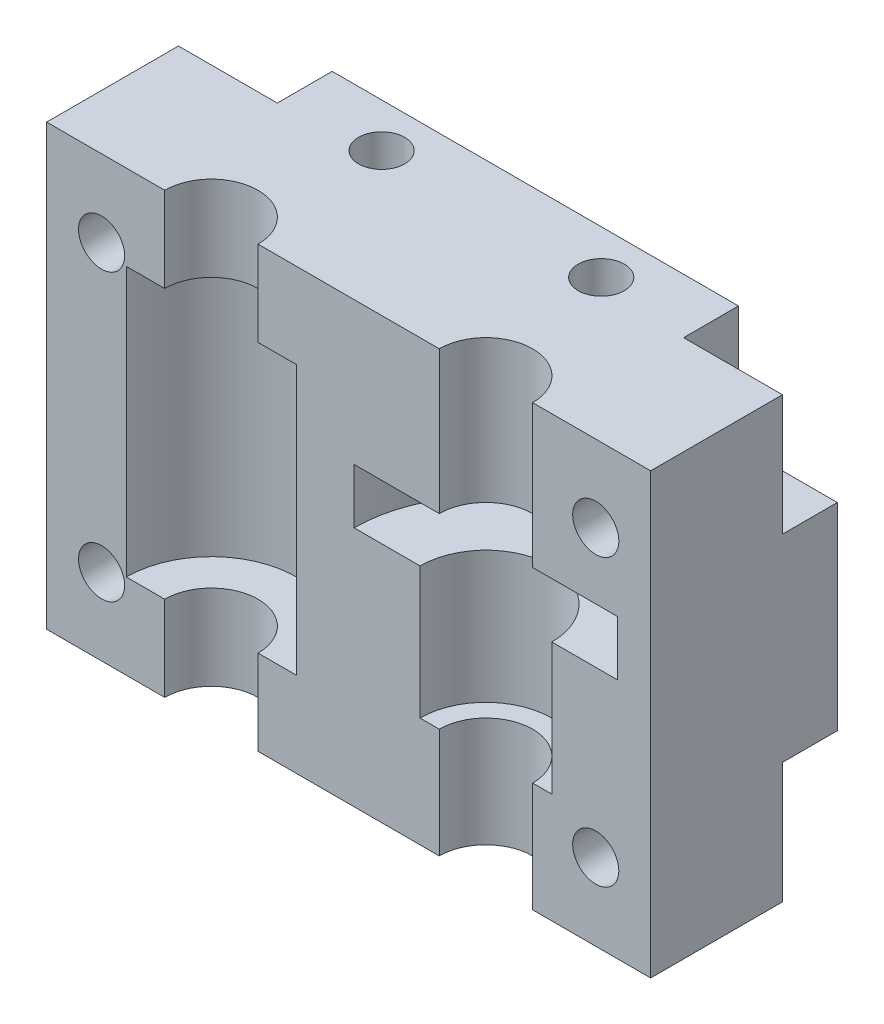
SolidWorks part; units mm, degrees
ref_plane "Plan de face" through (0, 0, 0) normal (0, 0, 1) x (1, 0, 0)
ref_plane "Plan de dessus" through (0, 0, 0) normal (0, 1, 0) x (1, 0, 0)
ref_plane "Plan de droite" through (0, 0, 0) normal (1, 0, 0) x (0, 0, -1)
sketch "Esquisse1" plane through (0, 0, 0) normal (0, 0, 1) x (1, 0, 0)
  line L1 (-27.5, -22.5) -> (27.5, -22.5)
  line L2 (-27.5, -22.5) -> (-27.5, 22.5)
  line L3 (-27.5, 22.5) -> (27.5, 22.5)
  line L4 (27.5, -22.5) -> (27.5, 22.5)
  line L5 (-27.5, -22.5) -> (27.5, 22.5) construction
  line L6 (-27.5, 22.5) -> (27.5, -22.5) construction
  point P0 (0, 0)
  dimension "D1" = 55
  dimension "D2" = 45
extrude "Boss.-Extru.1" add sketch "Esquisse1" along normal blind 12
sketch "Esquisse2" plane through (0, 22.5, 0) normal (0, 1, 0) x (1, 0, 0)
  line L0 (27.5, -12) -> (-27.5, -12) construction
  line L1 (-27.5, -12) -> (-27.5, 0) construction
  line L2 (27.5, -12) -> (27.5, 0) construction
  circle A0 centre (-12.5, -12) radius 4.25
  circle A1 centre (12.5, -12) radius 4.25
  dimension "D1" = 8.5
  dimension "D3" = 8.5
  dimension "D2" = 15
  dimension "D4" = 15
extrude "Enlèv. mat.-Extru.1" cut sketch "Esquisse2" against normal through all
sketch "Esquisse3" plane through (0, 0, 0) normal (0, 1, 0) x (1, 0, 0)
  circle A0 centre (-12.5, -12) radius 7.75
  dimension "D1" = 15.5
extrude "Enlèv. mat.-Extru.2" cut sketch "Esquisse3" against normal blind 12.25 and the other way blind 12.25
sketch "Esquisse9" plane through (0, 0, 12) normal (0, 0, 1) x (1, 0, 0)
  line L0 (-8.25, -22.5) -> (8.25, -22.5) construction
  line L1 (-30.9208, -30.2281) -> (30.1419, -30.2281)
  line L2 (-30.9208, -30.2281) -> (-30.9208, -18)
  line L3 (-30.9208, -18) -> (30.1419, -18)
  line L4 (30.1419, -30.2281) -> (30.1419, -18)
  line L5 (8.25, 22.5) -> (-8.25, 22.5) construction
  line L6 (31.3881, 26.1002) -> (-28.039, 26.1002)
  line L7 (31.3881, 26.1002) -> (31.3881, 18)
  line L8 (31.3881, 18) -> (-28.039, 18)
  line L9 (-28.039, 26.1002) -> (-28.039, 18)
  dimension "D1" = 4.5
  dimension "D2" = 4.5
extrude "Enlèv. mat.-Extru.7" cut sketch "Esquisse9" against normal blind 31
sketch "Sketch1" plane through (0, 0, 0) normal (0, 0, -1) x (-1, 0, 0)
  line L4 (-27.5, -18) -> (27.5, -18)
  line L5 (27.5, -18) -> (27.5, 18)
  line L6 (27.5, 18) -> (-27.5, 18)
  line L7 (-27.5, 18) -> (-27.5, -18)
  line L8 (-27.5, -18) -> (27.5, -18)
  line L9 (27.5, -18) -> (27.5, 18)
  line L10 (27.5, 18) -> (-27.5, 18)
  line L11 (-27.5, 18) -> (-27.5, -18)
  dimension "D1" = 0
extrude "Boss-Extrude1" add sketch "Sketch1" along normal blind 5
sketch "Sketch2" plane through (0, 0, 12) normal (0, 0, 1) x (1, 0, 0)
  line L0 (-27.5, 18) -> (-16.75, 18) construction
  line L1 (-27.5, 18) -> (-27.5, -18) construction
  line L2 (0, 18) -> (0, -18) construction
  line L3 (-8.25, 18) -> (8.25, 18) construction
  line L4 (8.25, -18) -> (-8.25, -18) construction
  line L5 (-27.5, 0) -> (27.5, 0) construction
  line L6 (27.5, -18) -> (27.5, 18) construction
  circle A0 centre (-22.5, 13) radius 2.1
  circle A1 centre (22.5, 13) radius 2.1
  circle A2 centre (22.5, -13) radius 2.1
  circle A3 centre (-22.5, -13) radius 2.1
  dimension "D1" = 4.2
  dimension "D2" = 5
  dimension "D3" = 5
extrude "Cut-Extrude1" cut sketch "Sketch2" against normal through all
sketch "Sketch3" plane through (0, 0, -5) normal (0, 0, -1) x (-1, 0, 0)
  circle A0 centre (-22.5, 13) radius 4
  circle A1 centre (22.5, 13) radius 4
  circle A2 centre (22.5, -13) radius 4
  circle A3 centre (-22.5, -13) radius 4
  dimension "D1" = 8
extrude "Cut-Extrude2" cut sketch "Sketch3" against normal blind 10
sketch "Sketch4" plane through (0, 0, -5) normal (0, 0, -1) x (-1, 0, 0)
  line L0 (-18.5, 13) -> (-18.5, 18)
  line L1 (-22.5, 9) -> (-27.5, 9)
  line L2 (-22.5, -9) -> (-27.5, -9)
  line L3 (-18.5, -13) -> (-18.5, -18)
  line L4 (-27.5, 18) -> (-27.5, -18)
  line L5 (-27.5, -18) -> (27.5, -18)
  line L6 (27.5, -18) -> (27.5, 18)
  line L7 (27.5, 18) -> (-27.5, 18)
  line L8 (-27.5, 18) -> (-27.5, 9)
  line L9 (-27.5, -18) -> (-18.5, -18)
  line L10 (27.5, -18) -> (27.5, -9)
  line L11 (27.5, 18) -> (18.5, 18)
  line L12 (18.5, -13) -> (18.5, -18)
  line L13 (22.5, -9) -> (27.5, -9)
  line L14 (22.5, 9) -> (27.5, 9)
  line L15 (18.5, 13) -> (18.5, 18)
  line L16 (-18.5, 18) -> (-27.5, 18)
  line L17 (-27.5, -9) -> (-27.5, -18)
  line L18 (18.5, -18) -> (27.5, -18)
  line L19 (27.5, 9) -> (27.5, 18)
  circle A0 centre (-22.5, 13) radius 4 construction
  circle A1 centre (-22.5, -13) radius 4 construction
  circle A2 centre (22.5, -13) radius 4 construction
  circle A3 centre (22.5, 13) radius 4 construction
  arc A4 (-18.5, 13) -> (-22.5, 9) centre (-22.5, 13) ccw
  arc A5 (-22.5, -9) -> (-18.5, -13) centre (-22.5, -13) ccw
  arc A6 (18.5, -13) -> (22.5, -9) centre (22.5, -13) ccw
  arc A7 (22.5, 9) -> (18.5, 13) centre (22.5, 13) ccw
  dimension "D1" = 0
extrude "Cut-Extrude3" cut sketch "Sketch4" against normal blind 5
sketch "Sketch5" plane through (0, 18, 0) normal (0, 1, 0) x (1, 0, 0)
  line L0 (-27.5, -12) -> (-27.5, 0) construction
  line L1 (27.5, 0) -> (27.5, 5) construction
  line L2 (-18.5, 5) -> (18.5, 5) construction
  circle A0 centre (-10, 1) radius 2.1
  circle A1 centre (10, 1) radius 2.1
  dimension "D1" = 4.2
  dimension "D2" = 4.2
  dimension "D3" = 17.5
  dimension "D4" = 17.5
  dimension "D5" = 4
  dimension "D6" = 4
extrude "Cut-Extrude4" cut sketch "Sketch5" against normal blind 10
sketch "Sketch7" plane through (0, 18, 0) normal (0, 1, 0) x (1, 0, 0)
  line L10 (18.5, 5) -> (-18.5, 5)
  line L11 (-18.5, 5) -> (-18.5, 0)
  line L12 (-18.5, 0) -> (-27.5, 0)
  line L13 (-27.5, 0) -> (-27.5, -12)
  line L14 (-27.5, -12) -> (-16.75, -12)
  line L15 (-8.25, -12) -> (8.25, -12)
  line L16 (16.75, -12) -> (27.5, -12)
  line L17 (27.5, -12) -> (27.5, 0)
  line L18 (27.5, 0) -> (18.5, 0)
  line L19 (18.5, 0) -> (18.5, 5)
  line L20 (18.5, 5) -> (-18.5, 5)
  line L21 (-18.5, 5) -> (-18.5, 0)
  line L22 (-18.5, 0) -> (-27.5, 0)
  line L23 (-27.5, 0) -> (-27.5, -12)
  line L24 (-27.5, -12) -> (-16.75, -12)
  line L25 (-8.25, -12) -> (8.25, -12)
  line L26 (16.75, -12) -> (27.5, -12)
  line L27 (27.5, -12) -> (27.5, 0)
  line L28 (27.5, 0) -> (18.5, 0)
  line L29 (18.5, 0) -> (18.5, 5)
  circle A0 centre (10, 1) radius 2.1 construction
  circle A1 centre (-10, 1) radius 2.1 construction
  arc A2 (-8.25, -12) -> (-16.75, -12) centre (-12.5, -12) ccw
  arc A3 (16.75, -12) -> (8.25, -12) centre (12.5, -12) ccw
  arc A4 (-8.25, -12) -> (-16.75, -12) centre (-12.5, -12) ccw
  arc A5 (16.75, -12) -> (8.25, -12) centre (12.5, -12) ccw
  circle A6 centre (10, 1) radius 2.1
  circle A7 centre (-10, 1) radius 2.1
  dimension "D1" = 0
extrude "Boss-Extrude4" add sketch "Sketch7" along normal blind 2
sketch "Sketch8" plane through (0, -18, 0) normal (0, -1, 0) x (1, 0, 0)
  line L10 (-27.5, 0) -> (-18.5, 0)
  line L11 (-18.5, 0) -> (-18.5, -5)
  line L12 (-18.5, -5) -> (18.5, -5)
  line L13 (18.5, -5) -> (18.5, 0)
  line L14 (18.5, 0) -> (27.5, 0)
  line L15 (27.5, 0) -> (27.5, 12)
  line L16 (27.5, 12) -> (16.75, 12)
  line L17 (8.25, 12) -> (-8.25, 12)
  line L18 (-16.75, 12) -> (-27.5, 12)
  line L19 (-27.5, 12) -> (-27.5, 0)
  line L20 (-27.5, 0) -> (-18.5, 0)
  line L21 (-18.5, 0) -> (-18.5, -5)
  line L22 (-18.5, -5) -> (18.5, -5)
  line L23 (18.5, -5) -> (18.5, 0)
  line L24 (18.5, 0) -> (27.5, 0)
  line L25 (27.5, 0) -> (27.5, 12)
  line L26 (27.5, 12) -> (16.75, 12)
  line L27 (8.25, 12) -> (-8.25, 12)
  line L28 (-16.75, 12) -> (-27.5, 12)
  line L29 (-27.5, 12) -> (-27.5, 0)
  circle A0 centre (-10, -1) radius 2.1 construction
  circle A1 centre (10, -1) radius 2.1 construction
  arc A2 (8.25, 12) -> (16.75, 12) centre (12.5, 12) ccw
  arc A3 (-16.75, 12) -> (-8.25, 12) centre (-12.5, 12) ccw
  arc A4 (8.25, 12) -> (16.75, 12) centre (12.5, 12) ccw
  arc A5 (-16.75, 12) -> (-8.25, 12) centre (-12.5, 12) ccw
  circle A6 centre (10, -1) radius 2.1
  circle A7 centre (-10, -1) radius 2.1
  dimension "D1" = 0
extrude "Boss-Extrude5" add sketch "Sketch8" along normal blind 2
ref_plane "Plan1" through (0, 2, 0) normal (0, 1, 0) x (1, 0, 0)
sketch "Sketch9" plane through (0, 0, -5) normal (0, 0, -1) x (-1, 0, 0)
  line L0 (-27.5, 20) -> (-27.5, 9) construction
  line L1 (-13.5, 16) -> (-6.5, 16)
  line L2 (-13.5, 16) -> (-13.5, 12.8)
  line L3 (-13.5, 12.8) -> (-6.5, 12.8)
  line L4 (-6.5, 16) -> (-6.5, 12.8)
  line L5 (-18.5, 20) -> (18.5, 20) construction
  line L6 (0, 20) -> (0, -9.1772) construction
  line L7 (13.5, 12.8) -> (6.5, 12.8)
  line L8 (6.5, 16) -> (6.5, 12.8)
  line L9 (13.5, 16) -> (6.5, 16)
  line L10 (13.5, 16) -> (13.5, 12.8)
  line L11 (-27.5, 0) -> (-8.3783, 0) construction
  line L12 (-27.5, 9) -> (-27.5, -9) construction
  line L13 (13.5, -16) -> (13.5, -12.8)
  line L14 (13.5, -16) -> (6.5, -16)
  line L15 (6.5, -16) -> (6.5, -12.8)
  line L16 (13.5, -12.8) -> (6.5, -12.8)
  line L17 (-13.5, -12.8) -> (-6.5, -12.8)
  line L18 (-6.5, -16) -> (-6.5, -12.8)
  line L19 (-13.5, -16) -> (-6.5, -16)
  line L20 (-13.5, -16) -> (-13.5, -12.8)
  point P4 (-10, 16)
  dimension "D1" = 7
  dimension "D2" = 17.5
  dimension "D3" = 4
  dimension "D4" = 3.2
extrude "Cut-Extrude6" cut sketch "Sketch9" against normal blind 8
ref_plane "Plane1" through (0, 0, 0) normal (-1, 0, 0) x (0, 0, 1)
mirror "Mirror1" [suppressed] about plane through (0, 0, 0) normal (-1, 0, 0)
sketch "Esquisse10" [suppressed] plane through (0, 0, -5) normal (0, 0, -1) x (-1, 0, 0)
  line L0 (27.5, -20) -> (-27.5, 20) construction
  line L2 (15, 5) -> (-15, 5)
  line L3 (15, 5) -> (15, -5)
  line L4 (15, -5) -> (-15, -5)
  line L5 (-15, 5) -> (-15, -5)
  line L6 (15, 5) -> (-15, -5) construction
  line L7 (15, -5) -> (-15, 5) construction
  point P4 (0, 0)
  dimension "D1" = 10
  dimension "D2" = 30
extrude "Boss.-Extru.2" [suppressed] add sketch "Esquisse10" along normal blind 80
fillet "Congé1" [suppressed] radius 10
sketch "Esquisse11" [suppressed] plane through (0, -5, 0) normal (0, -1, 0) x (1, 0, 0)
  line L0 (0, -5) -> (0, -85) construction
  line L1 (-18.5, -5) -> (18.5, -5) construction
  line L2 (5, -85) -> (-5, -85) construction
  circle A0 centre (0, -70) radius 4
  dimension "D1" = 8
  dimension "D2" = 15
extrude "Enlèv. mat.-Extru.8" [suppressed] cut sketch "Esquisse11" against normal through all
sketch "Esquisse12" plane through (0, 2, 0) normal (0, -1, 0) x (-1, 0, 0)
  circle A0 centre (-12.5, -12) radius 6
  dimension "D1" = 12
extrude "Enlèv. mat.-Extru.9" cut sketch "Esquisse12" along normal blind 12
sketch "Esquisse13" plane through (0, 2, 0) normal (0, -1, 0) x (-1, 0, 0)
  circle A0 centre (-12.5, -12) radius 12
  dimension "D1" = 24
extrude "Enlèv. mat.-Extru.10" cut sketch "Esquisse13" against normal blind 5
move or copy body "Body-Move/Copy1" [suppressed] bodies to move or copy 135
